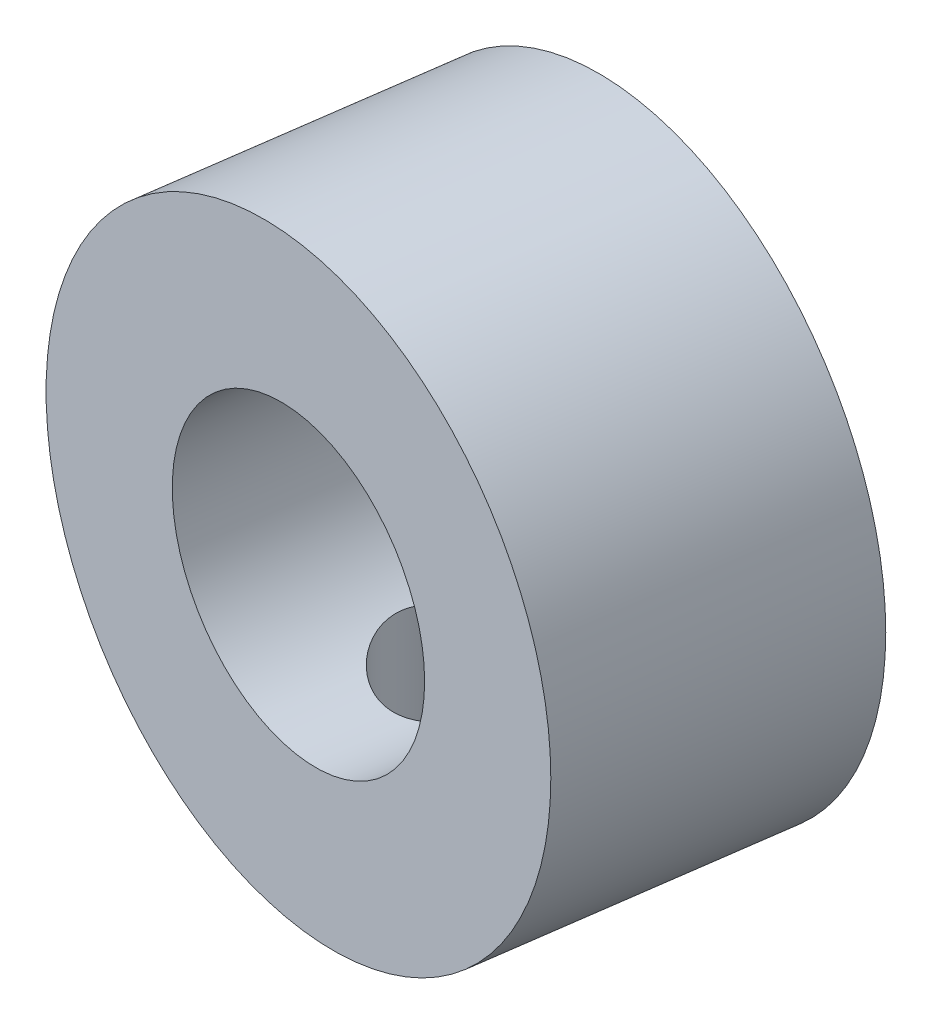
SolidWorks part; units mm, degrees
ref_plane "Front Plane" through (0, 0, 0) normal (0, 0, 1) x (1, 0, 0)
ref_plane "Top Plane" through (0, 0, 0) normal (0, 1, 0) x (1, 0, 0)
ref_plane "Right Plane" through (0, 0, 0) normal (1, 0, 0) x (0, 0, -1)
sketch "Sketch1" plane through (-29.9585, -0.0055, 37.9225) normal (0.9894, -0.0409, 0.1391) x (0.1393, 0, -0.9903)
  line L0 (22.0768, -11.1359) -> (73.3766, -11.1359) construction
  line L1 (50.2159, -4.7859) -> (56.5659, -4.7859) construction
  line L2 (50.2159, -4.7859) -> (50.2159, -17.4859) construction
  line L3 (50.2159, -17.4859) -> (56.5659, -17.4859) construction
  line L4 (56.5659, -4.7859) -> (56.5659, -17.4859) construction
  line L5 (50.2159, -11.1359) -> (56.5659, -11.1359)
  line L6 (50.2159, -4.7859) -> (56.5659, -4.7859)
  line L7 (50.2159, -14.3109) -> (50.2159, -17.4859)
  line L8 (50.2159, -17.4859) -> (56.5659, -17.4859)
  line L9 (56.5659, -14.3109) -> (56.5659, -17.4859)
  line L10 (38.8875, -14.3109) -> (56.5659, -14.3109) construction
  line L11 (50.2159, -14.3109) -> (56.5659, -14.3109)
revolve "Revolve1" add sketch "Sketch1" angle 360 about L5 region at (-23.1678, -15.8906, -15.0388)
ref_plane "Plane1" through (0, -17.482, 0) normal (0, -1, 0) x (-1, 0, 0)
sketch "Sketch2" plane through (0, -17.482, 0) normal (0, -1, 0) x (-1, 0, 0)
  line L0 (23.6742, 11.9038) -> (22.79, 18.1919) construction
  line L1 (23.6742, 11.9038) -> (22.79, 18.1919)
  point P2 (23.2321, 15.0478)
hole_wizard "#6-32 Tapped Hole1" positions "Sketch4" profile "Sketch5" tap size "#6-32" standard "ANSI Inch"
sketch "Sketch4" plane through (0, -17.482, 0) normal (0, -1, 0) x (-1, 0, 0)
  point P0 (23.2321, 15.0478)
sketch "Sketch5" plane through (-23.2321, -17.482, -15.0478) normal (1, 0, 0) x (0, 0, -1)
  line L0 (0, 0) -> (0, 7.1627)
  line L1 (0, 7.1627) -> (1.3525, 6.35)
  line L2 (1.3525, 6.35) -> (1.3525, 0)
  line L5 (1.3525, 0) -> (0, 0)
  line L10 (0, 7.1627) -> (-1.3526, 6.35) construction
  line L11 (0, -6.35) -> (0, 107.95) construction
  dimension "Tap Drill Dia." = 2.7051
  dimension "Tap Drill Depth" = 6.35
  dimension "Drill Angle" = 118
cosmetic thread "Hole Thread1" parameters "D1"=3.4775, "D2"=3.5052
